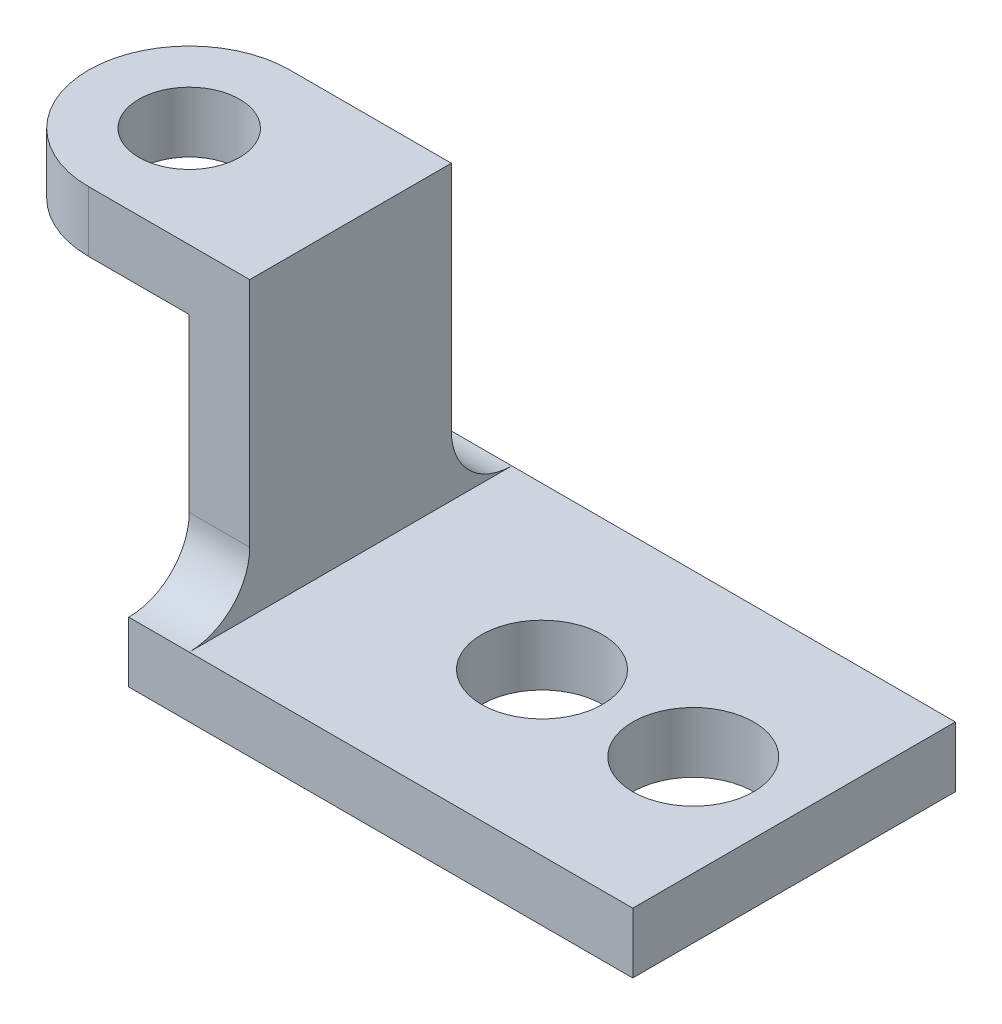
SolidWorks part; units mm, degrees
ref_plane "Front Plane" through (0, 0, 0) normal (0, 0, 1) x (1, 0, 0)
ref_plane "Top Plane" through (0, 0, 0) normal (0, 1, 0) x (1, 0, 0)
ref_plane "Right Plane" through (0, 0, 0) normal (1, 0, 0) x (0, 0, -1)
sketch "Sketch1" plane through (0, 0, 0) normal (0, 1, 0) x (1, 0, 0)
  line L1 (-50, -32) -> (50, -32)
  line L2 (-50, -32) -> (-50, 32)
  line L3 (-50, 32) -> (50, 32)
  line L4 (50, -32) -> (50, 32)
  line L5 (-50, -32) -> (50, 32) construction
  line L6 (-50, 32) -> (50, -32) construction
  point P0 (0, 0)
  dimension "D1" = 100
  dimension "D2" = 64
extrude "Boss-Extrude1" add sketch "Sketch1" along normal blind 12 contours L2 L1 L4 L3
sketch "Sketch2" plane through (0, 12, 0) normal (0, 1, 0) x (1, 0, 0)
  line L0 (-50, 0) -> (50, 0) construction
  line L1 (-50, -32) -> (-50, 32) construction
  line L2 (50, -32) -> (50, 32) construction
  circle A0 centre (0, 0) radius 12
  circle A1 centre (30, 0) radius 12
  point P10 (21.365, 0)
  dimension "D1" = 24
  dimension "D2" = 30
  dimension "D3" = 20
extrude "Cut-Extrude1" cut sketch "Sketch2" against normal through all both and the other way through all
sketch "Sketch3" plane through (0, 12, 0) normal (0, 1, 0) x (1, 0, 0)
  line L0 (-50, -32) -> (-50, 32) construction
  line L1 (-50, 20) -> (-38, 20)
  line L2 (-50, 20) -> (-50, -20)
  line L3 (-50, -20) -> (-38, -20)
  line L4 (-38, 20) -> (-38, -20)
  dimension "D1" = 40
  dimension "D2" = 20
  dimension "D3" = 12
extrude "Boss-Extrude2" add sketch "Sketch3" along normal blind 46
sketch "Sketch4" plane through (0, 58, 0) normal (0, 1, 0) x (1, 0, 0)
  line L0 (-50, 20) -> (-70, 20)
  line L1 (-50, -20) -> (-70, -20)
  line L4 (-50, 20) -> (-50, -20)
  line L5 (-50, -20) -> (-38, -20)
  line L6 (-38, -20) -> (-38, 20)
  line L7 (-38, 20) -> (-50, 20)
  line L9 (-50, -20) -> (-38, -20)
  line L10 (-38, -20) -> (-38, 20)
  line L11 (-38, 20) -> (-50, 20)
  arc A0 (-70, 20) -> (-70, -20) centre (-70, 0) ccw
  circle A1 centre (-70, 0) radius 10
  dimension "D2" = 40
  dimension "D4" = 20
  dimension "D3" = 32
  dimension "D1" = 0
extrude "Boss-Extrude3" add sketch "Sketch4" along normal blind 12
fillet "Fillet1" radius 12 2 edges at (-44, 12, -20) (-44, 12, 20)
